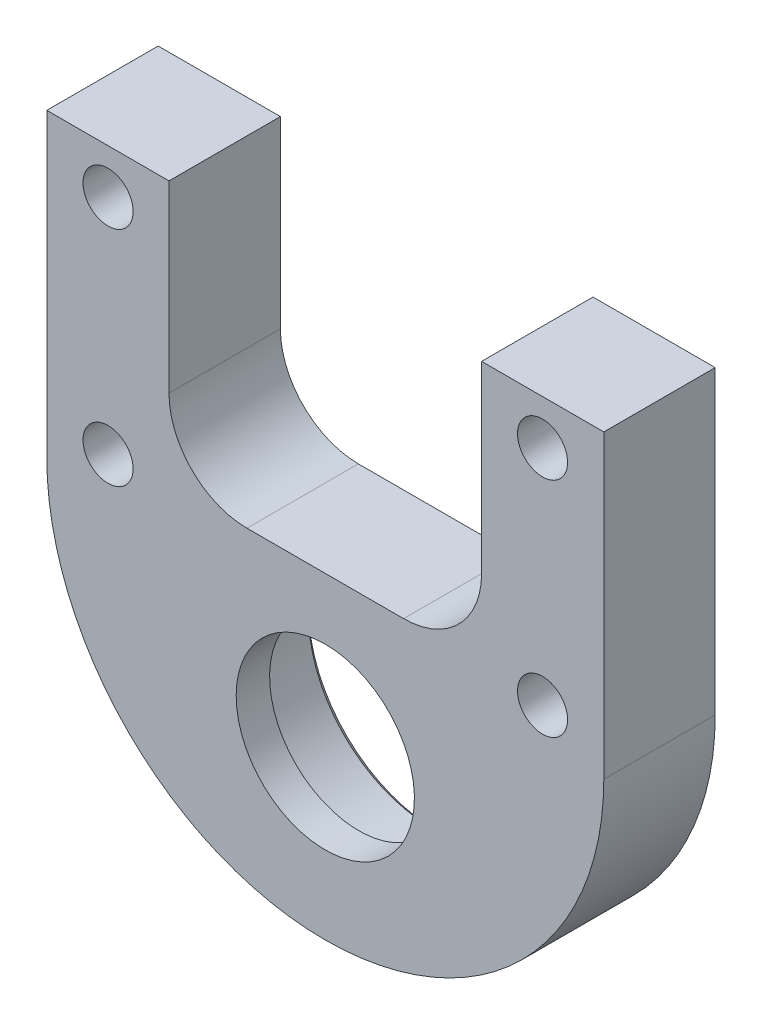
SolidWorks part; units mm, degrees
material "AISI 316 Annealed Stainless Steel Bar (SS)"
ref_plane "Front" through (0, 0, 0) normal (0, 0, 1) x (1, 0, 0)
ref_plane "Top" through (0, 0, 0) normal (0, 1, 0) x (1, 0, 0)
ref_plane "Right" through (0, 0, 0) normal (1, 0, 0) x (0, 0, -1)
sketch "Sketch1" plane through (0, 0, 0) normal (0, 0, 1) x (1, 0, 0)
  line L0 (0, 37) -> (0, 0) construction
  line L1 (-25, -15) -> (25, -15)
  line L2 (-25, -15) -> (-25, 37)
  line L3 (-25, 37) -> (25, 37)
  line L4 (25, -15) -> (25, 37)
  circle A0 centre (0, 0) radius 9.5 construction
  dimension "D3" = 19
  dimension "D5" = 15
  dimension "D1" = 52
  dimension "D2" = 50
extrude "Boss-Extrude1" add sketch "Sketch1" along normal blind 20
sketch "Sketch3" plane through (0, 0, 0) normal (1, 0, 0) x (0, 0, -1)
  line L0 (0, 0) -> (-20, 0)
  line L1 (-20, 0) -> (-20, 7.5)
  line L2 (-20, 7.5) -> (-17.75, 7.5)
  line L3 (-17.75, 7.5) -> (-17.75, 8)
  line L4 (-17.75, 8) -> (-7, 8)
  line L5 (-7, 8) -> (-7, 11)
  line L6 (-7, 11) -> (0, 11)
  line L7 (0, 37) -> (0, 0) construction
  line L8 (0, 11) -> (0, 0)
  line L9 (-20, -15) -> (-20, 37) construction
  dimension "D1" = 11
  dimension "D2" = 8
  dimension "D3" = 7.5
  dimension "D4" = 7
  dimension "D5" = 2.25
revolve "Cut-Revolve1" cut sketch "Sketch3" angle 360 about L0
hole_wizard "5/32 (0.15625) Diameter Hole1" positions "Sketch4" profile "Sketch5" hole size "5/32" standard "ANSI Inch" end condition up to next
sketch "Sketch4" plane through (25, 0, 0) normal (1, 0, 0) x (0, 0, -1)
  line L1 (0, 0) -> (-20, 0) construction
  line L2 (-20, -15) -> (-20, 37) construction
  point P0 (-12, 0)
  dimension "D1" = 8
sketch "Sketch5" plane through (25, 0, 12) normal (0, 1, 0) x (0, 0, -1)
  line L0 (0, 0) -> (0, 17)
  line L1 (0, 17) -> (1.9844, 17)
  line L2 (1.9844, 17) -> (1.9844, 0)
  line L5 (1.9844, 0) -> (0, 0)
  line L11 (0, -6.35) -> (0, 107.95) construction
  dimension "Thru Hole Dia." = 3.9688
  dimension "Thru Hole Depth" = 17
fillet "Fillet1" radius 5 1 edges at (0, 37, 20) profile chamfer
hole_wizard "#2-56 Tapped Hole1" positions "Sketch8" profile "Sketch9" tap size "#2-56" standard "ANSI Inch"
sketch "Sketch8" plane through (0, 0, 20) normal (0, 0, 1) x (1, 0, 0)
  line L0 (-14.5, 0) -> (14.5, 0)
  point P0 (-14.5, 0)
  point P2 (14.5, 0)
  dimension "D1" = 29
sketch "Sketch9" plane through (-14.5, 0, 20) normal (1, 0, 0) x (0, -1, 0)
  line L0 (0, 0) -> (0, 8.4542)
  line L1 (0, 8.4542) -> (0.889, 7.92)
  line L2 (0.889, 7.92) -> (0.889, 0)
  line L5 (0.889, 0) -> (0, 0)
  line L10 (0, 8.4542) -> (-0.889, 7.92) construction
  line L11 (0, -6.35) -> (0, 107.95) construction
  dimension "Tap Drill Dia." = 1.778
  dimension "Tap Drill Depth" = 7.92
  dimension "Drill Angle" = 118
cosmetic thread "Hole Thread1" parameters "D1"=6.2259, "D2"=2.1844
cosmetic thread "Hole Thread2" parameters "D1"=6.555, "D2"=2.1844
sketch "Sketch27" plane through (0, 0, 20) normal (0, 0, 1) x (1, 0, 0)
  line L5 (-25, -15) -> (25, -15)
  line L6 (-25, -15) -> (-25, 37)
  line L7 (-25, 37) -> (25, 37)
  line L8 (25, -15) -> (25, 37)
extrude "Cut-Extrude6" cut sketch "Sketch27" against normal blind 10
hole_wizard "#8 Clearance Hole1" positions "Sketch20" profile "Sketch21" hole size "#8" standard "ANSI Inch" end condition through all
sketch "Sketch20" plane through (0, 0, 10) normal (0, 0, 1) x (1, 0, 0)
  line L0 (-19.5, 37) -> (-19.5, 33) construction
  line L2 (-19.5, 33) -> (19.5, 33) construction
  line L3 (19.5, 33) -> (19.5, 37) construction
  line L6 (0, 33) -> (0, 37) construction
  line L9 (-19.5, 33) -> (-19.5, 13) construction
  line L10 (-19.5, 13) -> (19.5, 13) construction
  line L11 (19.5, 13) -> (19.5, 33) construction
  line L12 (25, 37) -> (-25, 37) construction
  point P0 (19.5, 33)
  point P5 (-19.5, 33)
  point P36 (-19.5, 13)
  point P39 (19.5, 13)
  dimension "D1" = 39
  dimension "D2" = 4
  dimension "D3" = 20
sketch "Sketch21" plane through (19.5, 33, 10) normal (1, 0, 0) x (0, -1, 0)
  line L0 (0, 0) -> (0, 10)
  line L1 (0, 10) -> (2.2479, 10)
  line L2 (2.2479, 10) -> (2.2479, 0)
  line L5 (2.2479, 0) -> (0, 0)
  line L11 (0, -6.35) -> (0, 107.95) construction
  dimension "Thru Hole Dia." = 4.4958
  dimension "Thru Hole Depth" = 10
hole_wizard "1/8 (0.1250) Dowel Hole1" positions "Sketch10" profile "Sketch11" hole size "1/8" standard "ANSI Inch"
sketch "Sketch10" plane through (0, 0, 0) normal (0, 0, -1) x (-1, 0, 0)
  line L11 (-19.5, 13) -> (-19.5, 33) construction
  point P0 (-19.5, 23)
sketch "Sketch11" plane through (19.5, 23, 0) normal (1, 0, 0) x (0, 1, 0)
  line L0 (0, 0) -> (0, 5.9539)
  line L1 (0, 5.9539) -> (1.5875, 5)
  line L2 (1.5875, 5) -> (1.5875, 0)
  line L5 (1.5875, 0) -> (0, 0)
  line L10 (0, 5.9539) -> (-1.5875, 5) construction
  line L11 (0, -6.35) -> (0, 107.95) construction
  dimension "Hole Dia." = 3.175
  dimension "Hole Depth" = 5
  dimension "Drill Angle" = 118
hole_wizard "1/8 (0.1250) Dowel Slot1" positions "Sketch12" profile "Sketch13" size "1/8" standard "ANSI Inch" slot yes
sketch "Sketch12" plane through (0, 0, 0) normal (0, 0, -1) x (-1, 0, 0)
  line L0 (17.5, 23) -> (21.5, 23) construction
  line L6 (19.5, 33) -> (19.5, 13) construction
  point P0 (19.5, 23)
  dimension "D1" = 4
sketch "Sketch13" plane through (-19.5, 23, 0) normal (1, 0, 0) x (0, 1, 0)
  line L0 (0, 0) -> (0, 5.9539)
  line L1 (0, 5.9539) -> (1.5875, 5)
  line L2 (1.5875, 5) -> (1.5875, 0)
  line L5 (1.5875, 0) -> (0, 0)
  line L10 (0, 5.9539) -> (-1.5875, 5) construction
  line L11 (0, -6.35) -> (0, 107.95) construction
  dimension "Hole Dia." = 3.175
  dimension "Hole Depth" = 5
  dimension "Drill Angle" = 118
sketch "Sketch22" plane through (0, 0, 0) normal (0, 0, -1) x (-1, 0, 0)
  circle A0 centre (0, 0) radius 10
  dimension "D1" = 20
chamfer "Chamfer1" distance 0.5 angle 45 1 edges at (0, 11, 0)
sketch "Sketch24" plane through (0, 0, 10) normal (0, 0, 1) x (1, 0, 0)
  line L0 (25, 37) -> (-25, 37) construction
  line L1 (-14.0313, 37) -> (14.0313, 37)
  line L2 (-14.0313, 37) -> (-14.0313, 20.5)
  line L3 (-7.0313, 13.5) -> (7.0313, 13.5)
  line L4 (14.0313, 37) -> (14.0313, 20.5)
  line L5 (0, 13.5) -> (0, 0) construction
  circle A0 centre (-19.5, 33) radius 2.2479 construction
  arc A1 (7.0313, 13.5) -> (14.0313, 20.5) centre (7.0313, 20.5) ccw
  arc A2 (-14.0313, 20.5) -> (-7.0313, 13.5) centre (-7.0313, 20.5) ccw
  circle A4 centre (0, 0) radius 11.5 construction
  dimension "D1" = 3.2208
  dimension "D2" = 7
  dimension "D3" = 2
extrude "Cut-Extrude5" cut sketch "Sketch24" against normal through all
fillet "Fillet3" radius 25 2 edges at (25, -15, 5) (-25, -15, 5)
